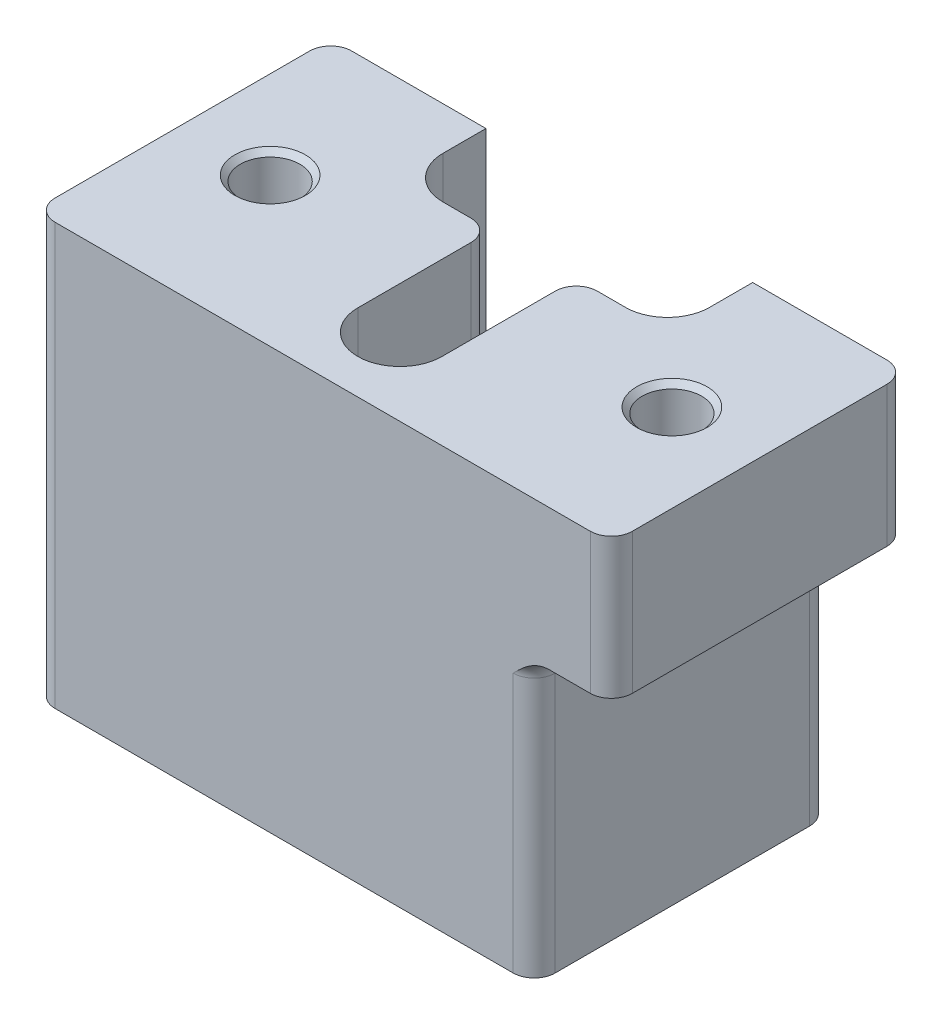
SolidWorks part; units mm, degrees
material "K110"
ref_plane "Front Plane" through (0, 0, 0) normal (0, 0, 1) x (1, 0, 0)
ref_plane "Top Plane" through (0, 0, 0) normal (0, 1, 0) x (1, 0, 0)
ref_plane "Right Plane" through (0, 0, 0) normal (1, 0, 0) x (0, 0, -1)
sketch "Sketch2" plane through (0, 0, 0) normal (0, 1, 0) x (1, 0, 0)
  line L1 (-41.12, -21.13) -> (41.12, -21.13)
  line L2 (-41.12, -21.13) -> (-41.12, 21.13)
  line L3 (-41.12, 21.13) -> (41.12, 21.13)
  line L4 (41.12, -21.13) -> (41.12, 21.13)
  line L5 (-41.12, -21.13) -> (41.12, 21.13) construction
  line L6 (-41.12, 21.13) -> (41.12, -21.13) construction
  point P0 (0, 0)
  dimension "D1" = 42.26
  dimension "D2" = 82.24
extrude "Boss-Extrude1" add sketch "Sketch2" against normal blind 60
fillet "Fillet1" radius 3 4 edges at (-41.12, -30, -21.13) (-41.12, -30, 21.13) (41.12, -30, -21.13) (41.12, -30, 21.13)
sketch "Sketch5" plane through (0, -60, 0) normal (0, -1, 0) x (1, 0, 0)
  line L0 (19, -21.13) -> (30.13, -21.13) construction
  line L1 (19, -15) -> (19, -21.13) construction
  line L2 (9, -9) -> (13, -9) construction
  line L3 (6, 10.13) -> (6, -6) construction
  line L4 (-6, -6) -> (-6, 10.13) construction
  line L5 (-13, -9) -> (-9, -9) construction
  line L6 (-19, -21.13) -> (-19, -15) construction
  line L7 (-41.12, -21.13) -> (-19, -21.13) construction
  line L8 (-41.12, -21.13) -> (-41.12, 21.13) construction
  line L9 (30.13, 21.13) -> (-41.12, 21.13) construction
  line L10 (30.13, -21.13) -> (30.13, 21.13) construction
  line L11 (19, -21.13) -> (30.13, -21.13)
  line L12 (19, -15) -> (19, -21.13)
  line L13 (9, -9) -> (13, -9)
  line L14 (6, 10.13) -> (6, -6)
  line L15 (-6, -6) -> (-6, 10.13)
  line L16 (-13, -9) -> (-9, -9)
  line L17 (-19, -21.13) -> (-19, -15)
  line L18 (-41.12, -21.13) -> (-19, -21.13)
  line L19 (-41.12, -21.13) -> (-41.12, 21.13)
  line L20 (30.13, 21.13) -> (-41.12, 21.13)
  line L21 (30.13, -21.13) -> (30.13, 21.13)
  arc A0 (19, -15) -> (13, -9) centre (13, -15) ccw construction
  arc A1 (6, -6) -> (9, -9) centre (9, -6) ccw construction
  arc A2 (6, 10.13) -> (-6, 10.13) centre (0, 10.13) ccw construction
  arc A3 (-9, -9) -> (-6, -6) centre (-9, -6) ccw construction
  arc A4 (-13, -9) -> (-19, -15) centre (-13, -15) ccw construction
  arc A5 (19, -15) -> (13, -9) centre (13, -15) ccw
  arc A6 (6, -6) -> (9, -9) centre (9, -6) ccw
  arc A7 (6, 10.13) -> (-6, 10.13) centre (0, 10.13) ccw
  arc A8 (-9, -9) -> (-6, -6) centre (-9, -6) ccw
  arc A9 (-13, -9) -> (-19, -15) centre (-13, -15) ccw
extrude "Cut-Extrude2" cut sketch "Sketch5" against normal up to surface (40 mm away) flip side to cut
sketch "Sketch6" plane through (0, -60, 0) normal (0, -1, 0) x (1, 0, 0)
  line L0 (-19, -21.13) -> (-19, -15) construction
  line L1 (-13, -9) -> (-9, -9) construction
  line L2 (-6, -6) -> (-6, 10.13) construction
  line L3 (6, 10.13) -> (6, -6) construction
  line L4 (9, -9) -> (13, -9) construction
  line L5 (19, -15) -> (19, -21.13) construction
  line L6 (-13, -9) -> (-9, -9)
  line L7 (-6, -6) -> (-6, 10.13)
  line L8 (6, 10.13) -> (6, -6)
  line L9 (9, -9) -> (13, -9)
  line L10 (19, -15) -> (19, -21.13)
  line L11 (-19, -21.13) -> (-19, -15)
  line L12 (-19, -21.13) -> (19, -21.13)
  arc A0 (-9, -9) -> (-6, -6) centre (-9, -6) ccw construction
  arc A1 (-13, -9) -> (-19, -15) centre (-13, -15) ccw construction
  arc A2 (6, 10.13) -> (-6, 10.13) centre (0, 10.13) ccw construction
  arc A3 (6, -6) -> (9, -9) centre (9, -6) ccw construction
  arc A4 (19, -15) -> (13, -9) centre (13, -15) ccw construction
  arc A5 (-9, -9) -> (-6, -6) centre (-9, -6) ccw
  arc A6 (6, 10.13) -> (-6, 10.13) centre (0, 10.13) ccw
  arc A7 (6, -6) -> (9, -9) centre (9, -6) ccw
  arc A8 (19, -15) -> (13, -9) centre (13, -15) ccw
  arc A9 (-13, -9) -> (-19, -15) centre (-13, -15) ccw
extrude "Cut-Extrude3" cut sketch "Sketch6" against normal through all
fillet "Fillet2" radius 3 2 edges at (30.13, -40, 21.13) (30.13, -40, -21.13)
fillet "Fillet3" radius 3 3 edges at (29.2513, -20, 20.2513) (29.2513, -20, -20.2513) (30.13, -20, 0)
hole_wizard "M10 Tapped Hole1" positions "Sketch11" profile "Sketch8" tap size "M10" standard "ISO"
sketch "Sketch11" plane through (0, 0, 0) normal (0, 1, 0) x (1, 0, 0)
  line L11 (-41.12, 0) -> (41.12, 0) construction
  line L12 (-41.12, 18.13) -> (-41.12, -18.13) construction
  line L13 (41.12, -18.13) -> (41.12, 18.13) construction
  point P0 (28.62, 0)
  point P2 (-28.62, 0)
  point P40 (0, 0)
  point P41 (0, 0)
  point P42 (0, 0)
  dimension "D1" = 12.5
  dimension "D2" = 12.5
sketch "Sketch8" plane through (28.62, 0, 0) normal (1, 0, 0) x (0, 0, 1)
  line L0 (0, 0) -> (0, 19.5)
  line L1 (0, 19.5) -> (4.25, 16.9463)
  line L2 (4.25, 16.9463) -> (4.25, 0.775)
  line L3 (4.25, 0.775) -> (5.025, 0)
  line L5 (5.025, 0) -> (0, 0)
  line L6 (-4.25, 0.775) -> (-5.025, 0) construction
  line L10 (0, 19.5) -> (-4.25, 16.9463) construction
  line L11 (0, -6.35) -> (0, 107.95) construction
  dimension "Tap Drill Dia." = 8.5
  dimension "Tap Drill Depth" = 19.5
  dimension "Near C'Sink Dia." = 10.05
  dimension "Near C'Sink Angle" = 90
  dimension "Drill Angle" = 118
cosmetic thread "Hole Thread1"
cosmetic thread "Hole Thread2"
